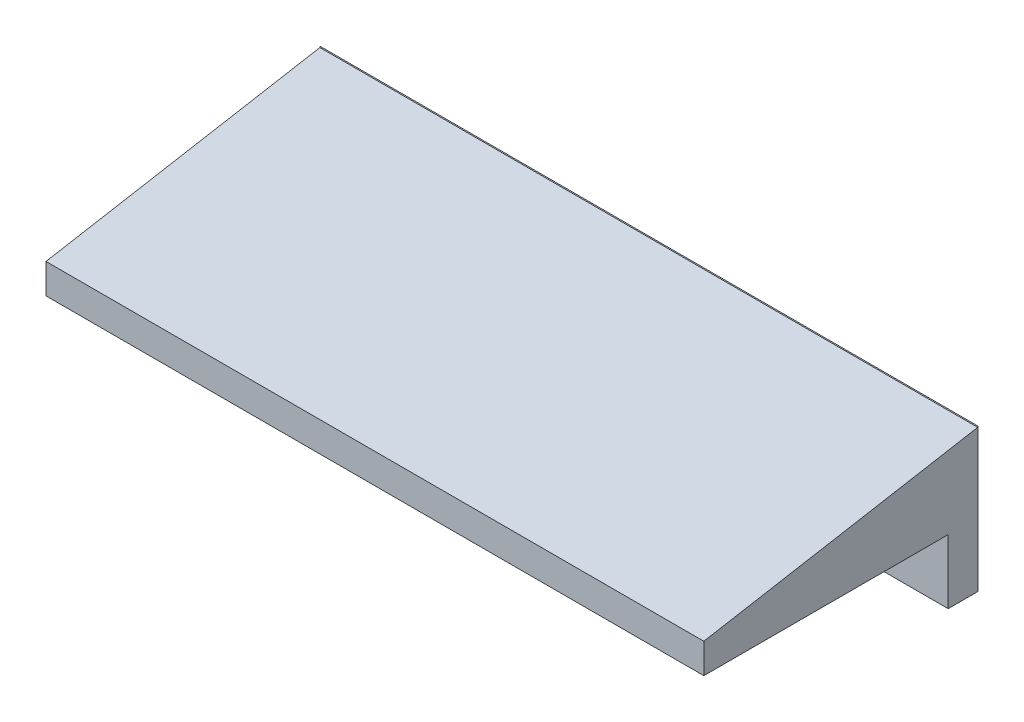
SolidWorks part; units mm, degrees
ref_plane "Front" through (0, 0, 0) normal (0, 0, 1) x (1, 0, 0)
ref_plane "Top" through (0, 0, 0) normal (0, 1, 0) x (1, 0, 0)
ref_plane "Right" through (0, 0, 0) normal (1, 0, 0) x (0, 0, -1)
sketch "Sketch1" plane through (0, 0, 0) normal (0, 1, 0) x (1, 0, 0)
  line L1 (-35, -13) -> (35, -13)
  line L2 (-35, -13) -> (-35, 13)
  line L3 (-35, 13) -> (35, 13)
  line L4 (35, -13) -> (35, 13)
  line L5 (-35, -13) -> (35, 13) construction
  line L6 (-35, 13) -> (35, -13) construction
  point P0 (0, 0)
  dimension "D1" = 26
  dimension "D2" = 70
extrude "Boss-Extrude1" add sketch "Sketch1" along normal blind 3.175
sketch "Sketch2" plane through (0, 0, -13) normal (0, 0, -1) x (-1, 0, 0)
  line L0 (35, 3.175) -> (-35, 3.175)
  line L1 (35, 3.175) -> (35, -6.825)
  line L2 (-35, 3.175) -> (-35, -6.825)
  line L3 (35, -6.825) -> (-35, -6.825)
  dimension "D1" = 10
  dimension "D2" = 70
extrude "Boss-Extrude2" add sketch "Sketch2" along normal blind 3.175
sketch "Sketch3" plane through (0, 0, -13) normal (0, 0, 1) x (1, 0, 0)
  line L0 (28.575, -3.825) -> (-14.914, -3.825)
  line L3 (-14.914, -3.825) -> (-28.575, -3.825)
  line L4 (35, -6.825) -> (-35, -6.825) construction
  circle A1 centre (-14.914, -3.825) radius 1.6
  circle A2 centre (28.575, -3.825) radius 1.6
  circle A3 centre (-28.575, -3.825) radius 1.6
  dimension "D3" = 13.661
  dimension "D1" = 3
extrude "Cut-Extrude1" cut sketch "Sketch3" against normal blind 3.175 contours A3 | A1 | A2
sketch "Sketch4" plane through (35, 0, 0) normal (1, 0, 0) x (0, 0, -1)
  line L0 (-13, 3.175) -> (16.1432, 8.3137)
  line L1 (-13, 3.175) -> (16.175, 3.175) construction
  line L2 (16.175, 3.175) -> (16.175, 8.4128)
  line L3 (16.175, 3.175) -> (-13, 3.175)
  line L4 (16.175, 8.4128) -> (16.1432, 8.3137)
  line L9 (-13, 0) -> (13, 0)
  line L10 (13, 0) -> (13, -6.825)
  line L11 (13, -6.825) -> (16.175, -6.825)
  line L12 (13, -6.825) -> (16.175, -6.825)
  line L13 (16.175, 3.175) -> (-13, 3.175)
  line L14 (-13, 3.175) -> (-13, 0)
  line L15 (-13, 0) -> (13, 0)
  line L16 (13, 0) -> (13, -6.825)
  line L20 (-13, 3.175) -> (-13, 0)
  line L22 (16.175, -6.825) -> (16.175, 3.175)
  line L23 (16.175, -6.825) -> (16.175, 3.175)
  line M6 (16.175, 3.175) -> (-13, 3.175)
  dimension "D1" = 10
  dimension "D2" = 0
extrude "Boss-Extrude3" add sketch "Sketch4" against normal blind 70 contours L2 L4 L0 M6 region at (35, 4.8898, -6.4502)
sketch "Sketch5" plane through (0, 0, -16.175) normal (0, 0, -1) x (-1, 0, 0)
  line L0 (-35, -6.825) -> (35, -6.825) construction
  line L1 (-25, -6.825) -> (3, -6.825)
  line L2 (-25, -6.825) -> (-25, 0)
  line L3 (-25, 0) -> (3, 0)
  line L4 (3, -6.825) -> (3, 0)
  line L5 (35, -6.825) -> (35, 8.4128) construction
  line L6 (-35, 8.4128) -> (-35, -6.825) construction
  dimension "D1" = 32
  dimension "D2" = 10
  dimension "D3" = 6.825
extrude "Cut-Extrude2" cut sketch "Sketch5" against normal blind 10
